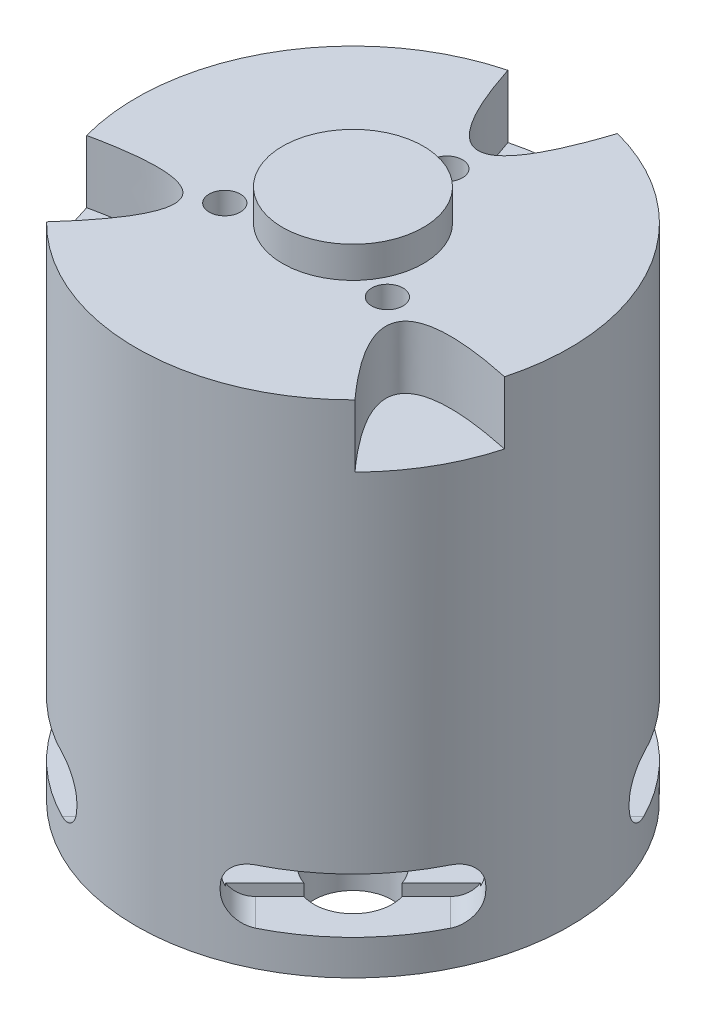
SolidWorks part; units mm, degrees
ref_plane "Front" through (0, 0, 0) normal (0, 0, 1) x (1, 0, 0)
ref_plane "Top" through (0, 0, 0) normal (0, 1, 0) x (1, 0, 0)
ref_plane "Right" through (0, 0, 0) normal (1, 0, 0) x (0, 0, -1)
sketch "Sketch1" plane through (0, 0, 0) normal (0, 1, 0) x (1, 0, 0)
  line L0 (0, 13.85) -> (0, -13.85) construction
  line L1 (-13.85, 0) -> (13.85, 0) construction
  line L2 (0, 0) -> (-13.4345, 13.4345) construction
  circle A0 centre (0, 0) radius 13.85
  circle A1 centre (0, 8) radius 1.5
  circle A2 centre (-9.5, 0) radius 1.5
  circle A3 centre (-6.7175, 6.7175) radius 2.5
  circle A4 centre (6.7175, 6.7175) radius 2.5
  circle A5 centre (9.5, 0) radius 1.5
  circle A6 centre (6.7175, -6.7175) radius 2.5
  circle A7 centre (0, -8) radius 1.5
  circle A8 centre (-6.7175, -6.7175) radius 2.5
  dimension "D1" = 27.7
  dimension "D2" = 3
  dimension "D3" = 3
  dimension "D6" = 5
  dimension "D4" = 9.5
  dimension "D5" = 8
  dimension "D7" = 9.5
extrude "Boss-Extrude1" add sketch "Sketch1" along normal blind 3
sketch "Sketch2" plane through (0, 3, 0) normal (0, 1, 0) x (1, 0, 0)
  circle A0 centre (0, 0) radius 12.35
  circle A1 centre (0, 0) radius 13.85
  circle A2 centre (0, 0) radius 13.85
  dimension "D1" = 0
  dimension "D2" = 1.5
extrude "Boss-Extrude2" add sketch "Sketch2" along normal blind 4
ref_plane "Plane1" through (-9.7934, 0, 9.7934) normal (-0.7071, 0, 0.7071) x (0, -1, 0)
sketch "Sketch3" plane through (-9.7934, 0, 9.7934) normal (-0.7071, 0, 0.7071) x (0, -1, 0)
  line L0 (0, 0) -> (-7, 0) construction
  line L1 (-7, 13.85) -> (-7, -13.85) construction
  line L2 (0, -13.85) -> (0, 13.85) construction
  line L3 (-4.15, 6) -> (-3.85, 6)
  line L4 (-5.75, 4.4) -> (-5.75, -4.4)
  line L5 (-4.15, -6) -> (-3.85, -6)
  line L6 (-2.25, 4.4) -> (-2.25, -4.4)
  line L7 (-5.75, 6) -> (-2.25, -6) construction
  line L8 (-5.75, -6) -> (-2.25, 6) construction
  arc A0 (-3.85, 6) -> (-2.25, 4.4) centre (-3.85, 4.4) cw
  arc A1 (-4.15, 6) -> (-5.75, 4.4) centre (-4.15, 4.4) ccw
  arc A2 (-2.25, -4.4) -> (-3.85, -6) centre (-3.85, -4.4) cw
  arc A3 (-4.15, -6) -> (-5.75, -4.4) centre (-4.15, -4.4) cw
  point P5 (-4, 0)
  dimension "D4" = 1.6
  dimension "D1" = 4
  dimension "D2" = 3.5
  dimension "D3" = 12
extrude "Cut-Extrude1" cut sketch "Sketch3" against normal blind 3.2
ref_axis "Axis1" through (0, 7, 0) along (0, -1, 0)
pattern_circular "CirPattern1" count 4 over 360 about axis through (0, 7, 0) along (0, -1, 0) of "Cut-Extrude1"
sketch "Sketch4" plane through (0, 7, 0) normal (0, 1, 0) x (1, 0, 0)
  circle A1 centre (0, 0) radius 13.85
  circle A2 centre (0, 0) radius 13.85
  dimension "D1" = 0
extrude "Boss-Extrude3" add sketch "Sketch4" along normal blind 25
sketch "Sketch5" plane through (0, 32, 0) normal (0, 1, 0) x (1, 0, 0)
  line L0 (0, 0) -> (0, 13.85) construction
  circle A0 centre (0, 0) radius 13.85 construction
  circle A1 centre (0, 6) radius 1
  circle A2 centre (5.1962, -3) radius 1
  circle A3 centre (-5.1962, -3) radius 1
  arc A4 (-13.3551, -3.6691) -> (-9.8551, -9.7313) centre (0, 0) ccw
  arc A5 (3.5, 13.4005) -> (-3.5, 13.4005) centre (0, 0) ccw
  arc A6 (9.8551, -9.7313) -> (13.3551, -3.6691) centre (0, 0) ccw
  spline S0 degree 2 poles (-3.5, 13.4005) (0, 2.5995) (3.5, 13.4005) knots 0 0 0 1 1 1
  spline S1 degree 2 poles (13.3551, -3.6691) (2.2513, -1.2998) (9.8551, -9.7313) knots 0 0 0 1 1 1
  spline S2 degree 2 poles (-9.8551, -9.7313) (-2.2513, -1.2998) (-13.3551, -3.6691) knots 0 0 0 1 1 1
  point P26 (0, 0)
  dimension "D1" = 2
  dimension "D2" = 6
  dimension "D3" = 3.5
  dimension "D4" = 3.5
  dimension "D5" = 2
  dimension "D6" = 3
extrude "Cut-Extrude2" cut sketch "Sketch5" against normal blind 4
sketch "Sketch6" plane through (0, 32, 0) normal (0, 1, 0) x (1, 0, 0)
  circle A0 centre (0, 0) radius 4.5
  dimension "D1" = 9
extrude "Boss-Extrude4" add sketch "Sketch6" along normal blind 2
sketch "Sketch7" plane through (0, 0, 0) normal (0, -1, 0) x (1, 0, 0)
  circle A0 centre (0, 0) radius 1.585
  dimension "D1" = 3.17
extrude "Boss-Extrude5" add sketch "Sketch7" along normal blind 3
